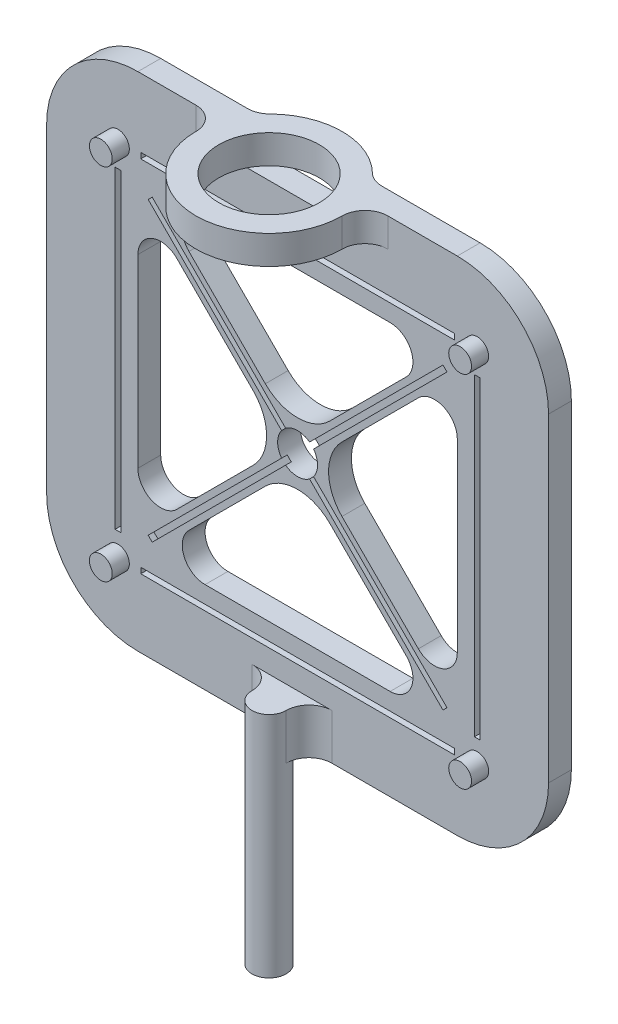
SolidWorks part; units mm, degrees
note: The reader was unsure of these and kept them because the rebuilt part matched: shared geometry of "Sketch3<3>".
material "ABS"
ref_plane "Front Plane" through (0, 0, 0) normal (0, 0, 1) x (1, 0, 0)
ref_plane "Top Plane" through (0, 0, 0) normal (0, 1, 0) x (1, 0, 0)
ref_plane "Right Plane" through (0, 0, 0) normal (1, 0, 0) x (0, 0, -1)
sketch "Sketch1" plane through (0, 0, 0) normal (0, 0, 1) x (1, 0, 0)
  line L1 (-25.4, 0) -> (-114.3, 0)
  line L2 (0, -25.4) -> (0, -114.3)
  line L3 (-25.4, -139.7) -> (-114.3, -139.7)
  line L4 (-139.7, -25.4) -> (-139.7, -114.3)
  arc A0 (-114.3, -139.7) -> (-139.7, -114.3) centre (-114.3, -114.3) cw
  arc A1 (0, -114.3) -> (-25.4, -139.7) centre (-25.4, -114.3) cw
  arc A2 (-25.4, 0) -> (0, -25.4) centre (-25.4, -25.4) cw
  arc A3 (-114.3, 0) -> (-139.7, -25.4) centre (-114.3, -25.4) ccw
  point P9 (0, -139.7)
  point P12 (0, 0)
  point P15 (-139.7, 0)
  dimension "D3" = 25.4
  dimension "D4" = 25.4
  dimension "D5" = 25.4
  dimension "D6" = 25.4
  dimension "D1" = 139.7
  dimension "D2" = 139.7
extrude "Boss-Extrude2" add sketch "Sketch1" along normal blind 6.35
sketch "Sketch2" plane through (0, 0, 6.35) normal (0, 0, 1) x (1, 0, 0)
  line L0 (-69.85, 0) -> (-69.85, -139.7) construction
  line L1 (-25.4, 0) -> (-114.3, 0) construction
  line L2 (-114.3, -139.7) -> (-25.4, -139.7) construction
  line L3 (-95.6021, -25.4) -> (-44.0979, -25.4)
  line L4 (-100.0923, -36.2401) -> (-78.8303, -57.5021)
  line L5 (-60.8697, -57.5021) -> (-39.6077, -36.2401)
  line L6 (-139.7, -69.85) -> (0, -69.85) construction
  line L7 (-139.7, -25.4) -> (-139.7, -114.3) construction
  line L8 (0, -114.3) -> (0, -25.4) construction
  line L9 (-69.85, -69.85) -> (-112.5391, -27.1609) construction
  line L10 (-57.5021, -78.8303) -> (-36.2401, -100.0923)
  line L11 (-25.4, -44.0979) -> (-25.4, -95.6021)
  line L12 (-36.2401, -39.6077) -> (-57.5021, -60.8697)
  line L13 (-78.8303, -82.1979) -> (-100.0923, -103.4599)
  line L14 (-44.0979, -114.3) -> (-95.6021, -114.3)
  line L15 (-39.6077, -103.4599) -> (-60.8697, -82.1979)
  line L16 (-82.1979, -60.8697) -> (-103.4599, -39.6077)
  line L17 (-114.3, -95.6021) -> (-114.3, -44.0979)
  line L18 (-103.4599, -100.0923) -> (-82.1979, -78.8303)
  circle A0 centre (-69.85, -69.85) radius 5.5563
  arc A1 (-44.0979, -25.4) -> (-39.6077, -36.2401) centre (-44.0979, -31.75) cw
  arc A2 (-95.6021, -25.4) -> (-100.0923, -36.2401) centre (-95.6021, -31.75) ccw
  arc A3 (-78.8303, -57.5021) -> (-60.8697, -57.5021) centre (-69.85, -48.5219) ccw
  arc A4 (-57.5021, -60.8697) -> (-57.5021, -78.8303) centre (-48.5219, -69.85) ccw
  arc A5 (-25.4, -95.6021) -> (-36.2401, -100.0923) centre (-31.75, -95.6021) cw
  arc A6 (-25.4, -44.0979) -> (-36.2401, -39.6077) centre (-31.75, -44.0979) ccw
  arc A7 (-60.8697, -82.1979) -> (-78.8303, -82.1979) centre (-69.85, -91.1781) ccw
  arc A8 (-95.6021, -114.3) -> (-100.0923, -103.4599) centre (-95.6021, -107.95) cw
  arc A9 (-44.0979, -114.3) -> (-39.6077, -103.4599) centre (-44.0979, -107.95) ccw
  arc A10 (-82.1979, -78.8303) -> (-82.1979, -60.8697) centre (-91.1781, -69.85) ccw
  arc A11 (-114.3, -44.0979) -> (-103.4599, -39.6077) centre (-107.95, -44.0979) cw
  arc A12 (-114.3, -95.6021) -> (-103.4599, -100.0923) centre (-107.95, -95.6021) ccw
  point P6 (-69.85, -69.85)
  point P12 (-69.85, -25.4)
  point P26 (-69.85, -66.4824)
  point P27 (0, 0)
  point P28 (0, 0)
  point P57 (-69.1755, -73.6995)
  point P58 (-69.85, -69.85)
  dimension "D1" = 11.1125
  dimension "D5" = 6.35
  dimension "D6" = 6.35
  dimension "D7" = 12.7
  dimension "D2" = 25.4
  dimension "D3" = 45
  dimension "D4" = 4.7625
  dimension "D8" = 4
extrude "Cut-Extrude1" cut sketch "Sketch2" against normal through all both and the other way through all
sketch "Sketch3" plane through (0, 0, 6.35) normal (0, 0, 1) x (1, 0, 0)
  line L0 (-69.85, -19.85) -> (-69.85, -119.85)
  line L1 (-119.85, -19.85) -> (-19.85, -19.85) construction
  line L2 (-119.85, -19.85) -> (-119.85, -119.85) construction
  line L3 (-119.85, -119.85) -> (-19.85, -119.85) construction
  line L4 (-19.85, -19.85) -> (-19.85, -119.85) construction
  line L9 (-19.85, -69.85) -> (-119.85, -69.85) construction
  line L10 (-119.85, -19.85) -> (-19.85, -119.85) construction
  line L11 (-119.85, -119.85) -> (-19.85, -19.85) construction
  line L12 (-111.431, -29.3915) -> (-29.3915, -111.431)
  line L17 (-29.3915, -111.431) -> (-28.269, -110.3085)
  line L18 (-28.269, -110.3085) -> (-110.3085, -28.269)
  line L19 (-110.3085, -28.269) -> (-111.431, -29.3915)
  line L20 (-110.3085, -111.431) -> (-111.431, -110.3085)
  line L21 (-29.3915, -28.269) -> (-28.269, -29.3915)
  line L22 (-111.431, -110.3085) -> (-29.3915, -28.269)
  line L23 (-28.269, -29.3915) -> (-110.3085, -111.431)
  line L24 (-119.0563, -26.2) -> (-119.0563, -113.5)
  line L25 (-113.5, -119.0562) -> (-26.2, -119.0562)
  line L26 (-113.5, -119.0562) -> (-113.5, -120.6437)
  line L27 (-113.5, -120.6437) -> (-26.2, -120.6437)
  line L28 (-26.2, -119.0562) -> (-26.2, -120.6437)
  line L29 (-119.0563, -26.2) -> (-120.6438, -26.2)
  line L30 (-120.6438, -26.2) -> (-120.6438, -113.5)
  line L31 (-119.0563, -113.5) -> (-120.6438, -113.5)
  line L32 (-26.2, -20.6437) -> (-113.5, -20.6437)
  line L33 (-26.2, -20.6437) -> (-26.2, -19.0562)
  line L34 (-26.2, -19.0562) -> (-113.5, -19.0562)
  line L35 (-113.5, -20.6437) -> (-113.5, -19.0562)
  line L36 (-20.6438, -113.5) -> (-20.6438, -26.2)
  line L37 (-20.6438, -113.5) -> (-19.0563, -113.5)
  line L38 (-19.0563, -113.5) -> (-19.0563, -26.2)
  line L39 (-20.6438, -26.2) -> (-19.0563, -26.2)
  circle A0 centre (-119.85, -19.85) radius 3.175
  circle A1 centre (-119.85, -119.85) radius 3.175
  circle A2 centre (-19.85, -119.85) radius 3.175
  circle A3 centre (-19.85, -19.85) radius 3.175
  text T0 "100 mm" font "Century Gothic" height in points 20
  point P8 (-69.85, -69.85)
  point P11 (-69.85, -69.85)
  point P17 (-28.8303, -110.8697)
  point P20 (-26.2, -119.85)
  point P21 (-110.8697, -28.8303)
  point P31 (0, 0)
  point P32 (0, 0)
  point P45 (-69.85, -69.85)
  dimension "D3" = 6.35
  dimension "D1" = 100
  dimension "D2" = 100
  dimension "D4" = 1.5875
  dimension "D5" = 12.7
  dimension "D6" = 12.7
  dimension "D7" = 6.35
  dimension "D8" = 6.35
  dimension "D9" = 1.5875
  dimension "D11" = 6.35
  dimension "D10" = 4
extrude "Cut-Extrude2" cut sketch "Sketch3" against normal blind 1.5875 and the other way through all
extrude "Boss-Extrude3" add sketch "Sketch3<3>" along normal blind 4.7625 contours A0 | A3 | A2 | A1
sketch "Sketch3<3>" plane through (0, 0, 6.35) normal (0, 0, 1) x (1, 0, 0) same geometry as "Sketch3"
sketch "Sketch5" plane through (0, 0, 0) normal (0, 1, 0) x (1, 0, 0)
  line L1 (-25.4, -6.35) -> (-114.3, -6.35) construction
  line L3 (-76.2, -12.7) -> (-76.2, -6.35) construction
  line L6 (-82.55, -6.35) -> (-60.325, -6.35)
  arc A0 (-76.2, -12.7) -> (-66.675, -12.7) centre (-71.4375, -12.7) ccw
  arc A3 (-60.325, -6.35) -> (-66.675, -12.7) centre (-60.325, -12.7) ccw
  arc A4 (-76.2, -12.7) -> (-82.55, -6.35) centre (-82.55, -12.7) ccw
  dimension "D1" = 4.7625
sketch "Sketch6" plane through (0, 0, 0) normal (0, 1, 0) x (1, 0, 0)
  line L0 (-98.1375, -6.35) -> (-90.7714, -6.35)
  line L1 (-25.4, -6.35) -> (-114.3, -6.35) construction
  line L2 (-25.4, 0) -> (-114.3, 0) construction
  line L3 (-90.1455, 0) -> (-87.3382, 0)
  line L4 (-52.7295, 0) -> (-55.5368, 0)
  line L5 (-44.7375, -6.35) -> (-52.1036, -6.35)
  circle A0 centre (-71.4375, -12.7) radius 14
  arc A1 (-52.1036, -6.35) -> (-55.5368, 0) centre (-71.4375, -12.7) ccw
  arc A2 (-44.7375, -6.35) -> (-51.0875, -12.7) centre (-44.7375, -12.7) ccw
  arc A3 (-91.7875, -12.7) -> (-98.1375, -6.35) centre (-98.1375, -12.7) ccw
  arc A4 (-90.1455, 0) -> (-85.6962, 1.8194) centre (-90.1455, 6.35) ccw
  arc A5 (-57.1788, 1.8194) -> (-52.7295, 0) centre (-52.7295, 6.35) ccw
  arc A6 (-57.1788, 1.8194) -> (-85.6962, 1.8194) centre (-71.4375, -12.7) ccw
  arc A7 (-87.3382, 0) -> (-90.7714, -6.35) centre (-71.4375, -12.7) ccw
  arc A8 (-91.7875, -12.7) -> (-51.0875, -12.7) centre (-71.4375, -12.7) ccw
  dimension "D1" = 28
  dimension "D2" = 6.35
  dimension "D3" = 12.7
extrude "Boss-Extrude7" add sketch "Sketch6" against normal blind 8
extrude "Boss-Extrude8" add sketch "Sketch5" along normal blind 12.7 from surface at -139.7 starting at face at (-69.85, -139.7, 3.175)
sketch "Sketch12" plane through (0, -139.7, 0) normal (0, -1, 0) x (1, 0, 0)
  circle A0 centre (-71.4375, 12.7) radius 4.7625
  dimension "D1" = 9.525
extrude "Boss-Extrude9" add sketch "Sketch12" along normal blind 50.8
sketch "Sketch13" plane through (0, 0, 0) normal (0, 1, 0) x (1, 0, 0)
  circle A0 centre (-71.4375, -12.7) radius 14
  dimension "D1" = 28
extrude "Cut-Extrude3" cut sketch "Sketch13" against normal up to surface (8 mm away) up to face at (-71.4375, -8, 14.8116)
